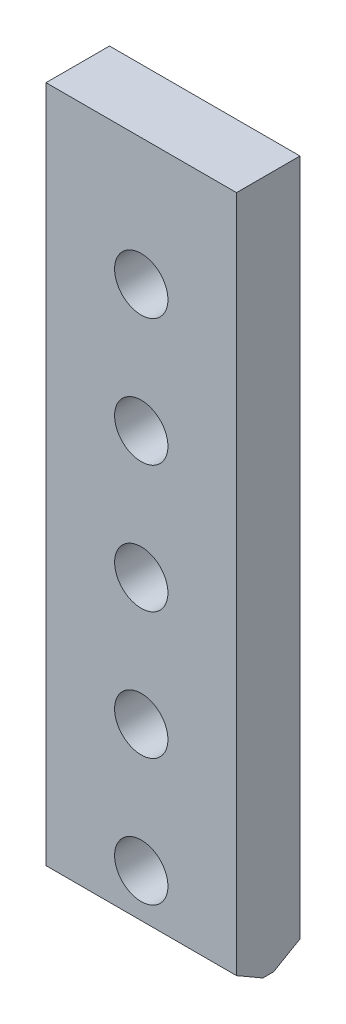
SolidWorks part; units mm, degrees
material "Простая углеродистая сталь"
ref_plane "Спереди" through (0, 0, 0) normal (0, 0, 1) x (1, 0, 0)
ref_plane "Сверху" through (0, 0, 0) normal (0, 1, 0) x (1, 0, 0)
ref_plane "Справа" through (0, 0, 0) normal (1, 0, 0) x (0, 0, -1)
sketch "Эскиз1" plane through (0, 0, 0) normal (0, 0, 1) x (1, 0, 0)
  line L1 (0, 0) -> (75, 0)
  line L2 (0, 0) -> (0, 273)
  line L3 (0, 273) -> (75, 273)
  line L4 (75, 0) -> (75, 273)
  point P5 (37.5, 273)
  dimension "D1" = 273
  dimension "D2" = 75
extrude "Бобышка-Вытянуть1" add sketch "Эскиз1" along normal blind 25
sketch "Эскиз2" plane through (0, 0, 25) normal (0, 0, 1) x (1, 0, 0)
  line L0 (0, 0) -> (75, 0) construction
  line L1 (75, 0) -> (75, 273) construction
  circle A0 centre (37.5, 23) radius 10.5
  circle A1 centre (37.5, 73) radius 10.5
  circle A2 centre (37.5, 123) radius 10.5
  circle A3 centre (37.5, 173) radius 10.5
  circle A4 centre (37.5, 223) radius 10.5
  dimension "D1" = 5
  dimension "D2" = 23
  dimension "D3" = 37.5
  dimension "D4" = 21
extrude "Вырез-Вытянуть1" cut sketch "Эскиз2" against normal through all
chamfer "Фаска1" distance 6 angle 60 1 edges at (37.5, 0, 0) first distance on face at (48, 73, 0)
chamfer "Фаска2" distance 6 angle 60 1 edges at (37.5, 0, 25) first distance on face at (48, 73, 25)
